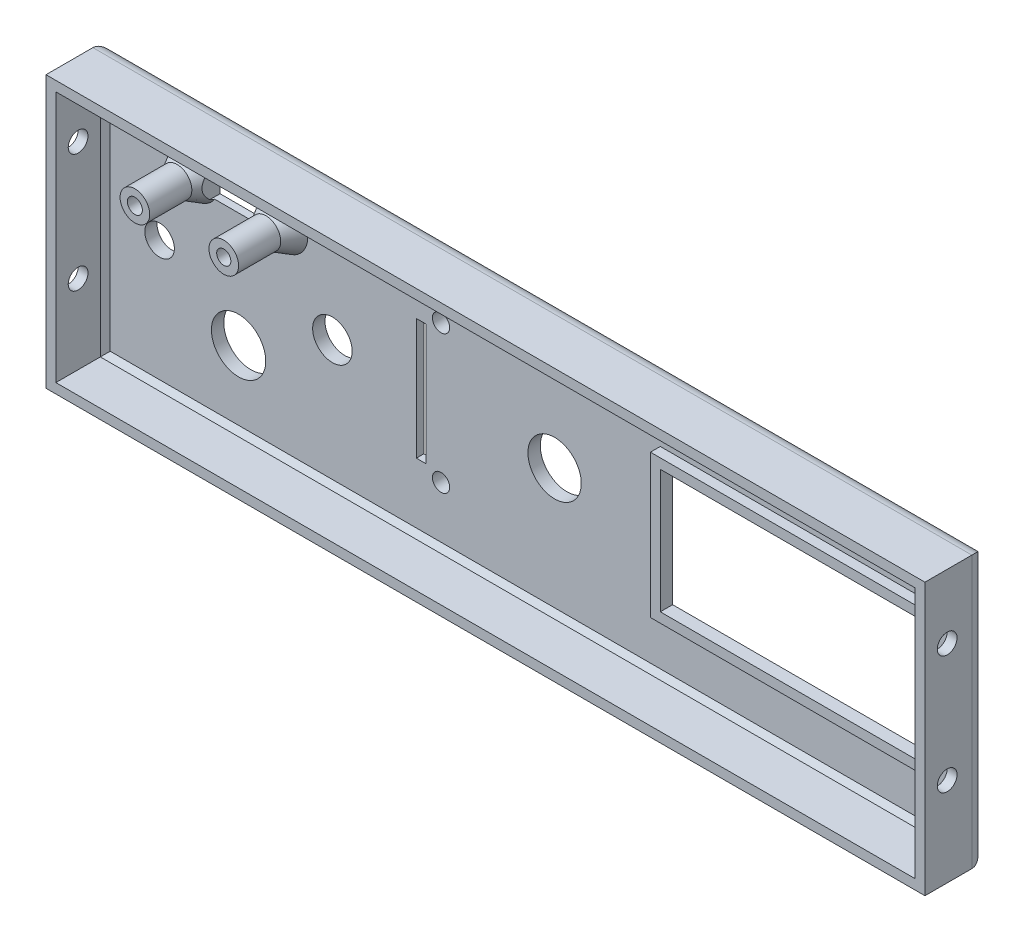
SolidWorks part; units mm, degrees
ref_plane "Спереди" through (0, 0, 0) normal (0, 0, 1) x (1, 0, 0)
ref_plane "Сверху" through (0, 0, 0) normal (0, 1, 0) x (1, 0, 0)
ref_plane "Справа" through (0, 0, 0) normal (1, 0, 0) x (0, 0, -1)
sketch "Эскиз1" plane through (0, 0, 0) normal (0, 0, 1) x (1, 0, 0)
  line L1 (-87, 25.5) -> (87, 25.5)
  line L2 (-87, 25.5) -> (-87, -25.5)
  line L3 (-87, -25.5) -> (87, -25.5)
  line L4 (87, 25.5) -> (87, -25.5)
  line L5 (-87, 25.5) -> (87, -25.5) construction
  line L6 (-87, -25.5) -> (87, 25.5) construction
  point P0 (0, 0)
  dimension "D1" = 174
  dimension "D2" = 51
extrude "Вытянуть-Тонкостенный1" add sketch "Эскиз1" along normal blind 10 thin thin type one direction wall 2
sketch "Эскиз4" plane through (0, 0, 0) normal (0, 0, -1) x (-1, 0, 0)
  line L1 (89, -27.5) -> (-89, -27.5)
  line L2 (89, -27.5) -> (89, 27.5)
  line L3 (89, 27.5) -> (-89, 27.5)
  line L4 (-89, -27.5) -> (-89, 27.5)
extrude "Бобышка-Вытянуть2" add sketch "Эскиз4" along normal blind 2.5
sketch "Эскиз5" plane through (0, 0, -2.5) normal (0, 0, -1) x (-1, 0, 0)
  line L0 (-99.6943, 0) -> (99.6943, 0)
  line L4 (54.75, 18.25) -> (65.25, 18.25)
  line L5 (54.75, 18.25) -> (54.75, 12.75)
  line L6 (54.75, 12.75) -> (65.25, 12.75)
  line L7 (65.25, 18.25) -> (65.25, 12.75)
  line L8 (54.75, 18.25) -> (65.25, 12.75) construction
  line L9 (54.75, 12.75) -> (65.25, 18.25) construction
  point P4 (0, 0)
  point P10 (60, 15.5)
extrude "Вырез-Вытянуть1" cut sketch "Эскиз5" against normal blind 2.5 contours L7 L4 L5 L6 region at (-60, 15.5, -2.5)
sketch "Эскиз7" plane through (0, 0, 0) normal (0, 0, 1) x (1, 0, 0)
  line L0 (-69, 15.5) -> (-51, 15.5) construction
  line L1 (-60, 12.75) -> (-60, 38.329) construction
  line L2 (-54.75, 12.75) -> (-65.25, 12.75) construction
  line L3 (-69, 15.5) -> (-69, 33.9874) construction
  line L6 (-51, 15.5) -> (-51, 34.7395) construction
  circle A0 centre (-51, 15.5) radius 3
  circle A1 centre (-69, 15.5) radius 3
  dimension "D1" = 9
  dimension "D2" = 9
extrude "Бобышка-Вытянуть3" add sketch "Эскиз7" along normal blind 12
sketch "Эскиз8" plane through (0, 0, 12) normal (0, 0, 1) x (1, 0, 0)
  line L0 (-72, 15.5) -> (-44.9054, 15.5) construction
  line L2 (-51, 18.5) -> (-51, 7.9878) construction
  line L4 (-69.1366, 7.9878) -> (-69.1366, 21.896) construction
  circle A0 centre (-69, 15.5) radius 3 construction
  circle A1 centre (-69, 15.5) radius 3 construction
  circle A2 centre (-51, 15.5) radius 3 construction
  circle A3 centre (-51, 15.5) radius 3 construction
  circle A4 centre (-69, 15.5) radius 1.5173
  circle A5 centre (-51, 15.5) radius 1.4341
extrude "Вырез-Вытянуть2" cut sketch "Эскиз8" against normal blind 8
sketch "Эскиз9" plane through (0, 0, -2.5) normal (0, 0, -1) x (-1, 0, 0)
  line L0 (60, 18.25) -> (60, -39.25) construction
  line L1 (54.75, 18.25) -> (65.25, 18.25) construction
  line L2 (-107.013, -12.5) -> (126.1089, -12.5) construction
  line L3 (126.1089, -12.5) -> (126.1089, 17.3777) construction
  circle A0 centre (60, -10.5) radius 5.5
  dimension "D2" = 17
  dimension "D1" = 15
extrude "Вырез-Вытянуть3" cut sketch "Эскиз9" against normal blind 8
sketch "Эскиз10" plane through (0, 0, -2.5) normal (0, 0, -1) x (-1, 0, 0)
  line L0 (19, 34.8185) -> (19, -39.1882) construction
  line L1 (-89, 0) -> (112.0403, 0) construction
  line L2 (-89, 27.5) -> (-89, -27.5) construction
  line L3 (7.1273, 14) -> (41.6077, 14) construction
  line L4 (7.1273, -14) -> (41.6077, -14) construction
  circle A0 centre (19, 14) radius 1.75
  circle A1 centre (19, -14) radius 1.75
  dimension "D1" = 70
  dimension "D2" = 14
  dimension "D3" = 14
extrude "Вырез-Вытянуть4" cut sketch "Эскиз10" against normal blind 8
sketch "Эскиз12" plane through (0, 0, -2.5) normal (0, 0, -1) x (-1, 0, 0)
  line L0 (0, 0) -> (84.374, 0) construction
  line L1 (19, 14) -> (19, 27.5) construction
  line L2 (89, 27.5) -> (-89, 27.5) construction
  line L3 (23, 0) -> (23, 27.5) construction
  line L4 (20.7098, 13.6272) -> (33.1859, 13.6272) construction
  line L5 (19, -12.25) -> (33.4448, -12.25) construction
  line L7 (22, 12.25) -> (24, 12.25)
  line L8 (22, 12.25) -> (22, -12.25)
  line L9 (22, -12.25) -> (24, -12.25)
  line L10 (24, 12.25) -> (24, -12.25)
  line L11 (22, 12.25) -> (24, -12.25) construction
  line L12 (22, -12.25) -> (24, 12.25) construction
  circle A0 centre (19, 14) radius 1.75 construction
  circle A1 centre (19, -14) radius 1.75 construction
  dimension "D1" = 4
  dimension "D2" = 2
extrude "Вырез-Вытянуть5" cut sketch "Эскиз12" against normal blind 8
sketch "Эскиз13" plane through (0, 0, -2.5) normal (0, 0, -1) x (-1, 0, 0)
  line L0 (-4, -33.8219) -> (-4, 43.2368) construction
  line L1 (-89, 0) -> (16.8794, 0) construction
  line L2 (-89, 27.5) -> (-89, -27.5) construction
  circle A0 centre (-4, 0) radius 5.4
  dimension "D1" = 4
extrude "Вырез-Вытянуть6" cut sketch "Эскиз13" against normal blind 8
sketch "Эскиз15" plane through (0, 0, -2.5) normal (0, 0, -1) x (-1, 0, 0)
  line L0 (0, 0) -> (-107.8488, 0) construction
  line L1 (-79, 31.1202) -> (-79, -32.9625) construction
  line L2 (-94.8238, 12.5) -> (-23.9681, 12.5) construction
  line L3 (-92.8701, -12.5) -> (-23.9681, -12.5) construction
  line L4 (-26, 31.1202) -> (-26, -20.3283) construction
  line L6 (-79, 12.5) -> (-27.4, 12.5)
  line L7 (-79, 12.5) -> (-79, -12.5)
  line L8 (-79, -12.5) -> (-27.4, -12.5)
  line L9 (-27.4, 12.5) -> (-27.4, -12.5)
  dimension "D1" = 10
  dimension "D2" = 12.5
  dimension "D3" = 12.5
  dimension "D4" = 51.6
extrude "Вырез-Вытянуть7" cut sketch "Эскиз15" against normal blind 8
sketch "Эскиз16" plane through (0, 0, 0) normal (0, 0, 1) x (1, 0, 0)
  line L1 (27.4, 12.5) -> (79, 12.5)
  line L2 (27.4, 12.5) -> (27.4, -12.5)
  line L3 (27.4, -12.5) -> (79, -12.5)
  line L4 (79, 12.5) -> (79, -12.5)
extrude "Вытянуть-Тонкостенный2" add sketch "Эскиз16" along normal blind 2 thin thin type one direction wall 2
chamfer "Фаска1" distance 2 angle 45 4 edges at (53.2, -12.5, -2.5) (27.4, 0, -2.5) (53.2, 12.5, -2.5) (79, 0, -2.5)
chamfer "Фаска2" distance 1 angle 45 4 edges at (-23, -12.25, -2.5) (-22, 0, -2.5) (-23, 12.25, -2.5) (-24, 0, -2.5)
chamfer "Фаска3" distance 1 angle 45 4 edges at (-65.25, 15.5, -2.5) (-60, 12.75, -2.5) (-54.75, 15.5, -2.5) (-60, 18.25, -2.5)
chamfer "Фаска4" distance 2 angle 60 2 edges at (-54, 15.5, 0) (-72, 15.5, 0) first distance on face at (-60, 15.5, 0)
chamfer "Фаска5" distance 1 angle 45 4 edges at (-87, 0, 0) (0, 25.5, 0) (87, 0, 0) (0, -25.5, 0)
fillet "Скругление1" radius 3 4 edges at (-89, 0, -2.5) (0, -27.5, -2.5) (0, 27.5, -2.5) (89, 0, -2.5)
sketch "Эскиз17" plane through (0, 0, -2.5) normal (0, 0, -1) x (-1, 0, 0)
  line L0 (-89.5147, 0) -> (89, 0) construction
  line L1 (89, 27.5) -> (89, -27.5) construction
  line L2 (41, 30.5864) -> (41, -33.103) construction
  circle A0 centre (41, 0) radius 4
  dimension "D1" = 48
extrude "Вырез-Вытянуть8" cut sketch "Эскиз17" against normal blind 10
sketch "Эскиз18" plane through (89, 0, 0) normal (1, 0, 0) x (0, 0, -1)
  line L0 (-22.2983, 14.5) -> (16.8946, 14.5) construction
  line L2 (-5.5, 32.6742) -> (-5.5, -32.2436) construction
  line L3 (2.5, -24.5) -> (2.5, 35.4733) construction
  line L4 (-20.3604, -9.5) -> (16.8946, -9.5) construction
  circle A0 centre (-5.5, 14.5) radius 2
  circle A1 centre (-5.5, -9.5) radius 2
  dimension "D3" = 37
  dimension "D1" = 13
  dimension "D2" = 8
extrude "Вырез-Вытянуть9" cut sketch "Эскиз18" against normal blind 10
sketch "Эскиз19" plane through (-89, 0, 0) normal (-1, 0, 0) x (0, 0, 1)
  circle A0 centre (5.5, 14.5) radius 2
  circle A1 centre (5.5, -9.5) radius 2
extrude "Вырез-Вытянуть10" cut sketch "Эскиз19" against normal blind 10
sketch "Эскиз20" plane through (0, 0, -2.5) normal (0, 0, -1) x (-1, 0, 0)
  line L0 (-3.7707, 0) -> (94.262, 0) construction
  line L1 (76, 30.6733) -> (76, -34.3255) construction
  line L2 (89, -27.5) -> (89, 30.6733) construction
  circle A0 centre (76, 0) radius 3
  dimension "D1" = 13
extrude "Вырез-Вытянуть11" cut sketch "Эскиз20" against normal blind 10
equation "\"D2@Эскиз7\"=\"D1@Эскиз7\""
equation "\"D3@Эскиз15\"=\"D2@Эскиз15\""
